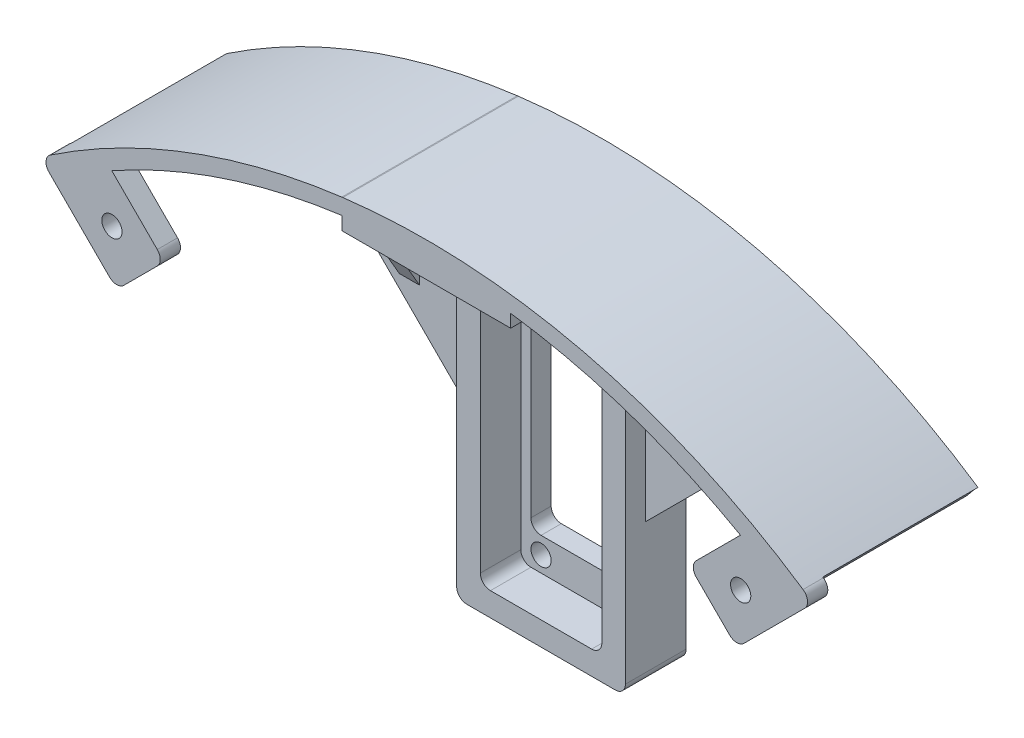
SolidWorks part; units mm, degrees
material "ABS"
ref_plane "Alzado" through (0, 0, 0) normal (0, 0, 1) x (1, 0, 0)
ref_plane "Planta" through (0, 0, 0) normal (0, 1, 0) x (1, 0, 0)
ref_plane "Vista lateral" through (0, 0, 0) normal (1, 0, 0) x (0, 0, -1)
sketch "Croquis1" plane through (0, 0, 0) normal (0, 0, 1) x (1, 0, 0)
  circle A0 centre (0, 0) radius 100
  dimension "D1" = 200
extrude "Saliente-Extruir1" add sketch "Croquis1" along normal blind 3
sketch "Croquis3" plane through (0, 0, 3) normal (0, 0, 1) x (1, 0, 0)
  line L0 (0, 0) -> (190, 0) construction
  circle A0 centre (190, 0) radius 110
  dimension "D1" = 220
  dimension "D2" = 190
extrude "Cortar-Extruir1" cut sketch "Croquis3" against normal blind 3
fillet "Redondeo1" radius 10 2 edges at (89.4737, -44.6594, 1.5) (89.4737, 44.6594, 1.5)
sketch "Croquis5" plane through (0, 0, 3) normal (0, 0, 1) x (1, 0, 0)
  line L0 (0, -100) -> (0, 100) construction
  line L1 (-100, 0) -> (80, 0) construction
  line L2 (0, 0) -> (-70.7107, -70.7107) construction
  line L3 (-70.7107, -70.7107) -> (70.7107, 70.7107) construction
  line L4 (0, 0) -> (-70.7107, 70.7107) construction
  line L5 (-70.7107, 70.7107) -> (70.7107, -70.7107) construction
  line L6 (-70.7107, -70.7107) -> (-58.3363, -83.085) construction
  line L9 (-58.3363, -83.085) -> (-83.085, -58.3363)
  line L11 (-83.085, -58.3363) -> (-65.4074, -40.6586)
  line L12 (-65.4074, -40.6586) -> (-40.6586, -65.4074)
  line L13 (-40.6586, -65.4074) -> (-58.3363, -83.085)
  line L14 (-70.7107, 70.7107) -> (-83.085, 58.3363) construction
  line L15 (-83.085, 58.3363) -> (-100, 0) construction
  line L17 (-83.085, 58.3363) -> (-58.3363, 83.085)
  line L18 (-58.3363, 83.085) -> (-40.6586, 65.4074)
  line L19 (-40.6586, 65.4074) -> (-65.4074, 40.6586)
  line L20 (-65.4074, 40.6586) -> (-83.085, 58.3363)
  line L22 (70.7107, -70.7107) -> (58.3363, -83.085) construction
  line L23 (58.3363, -83.085) -> (0, -100) construction
  line L24 (58.3363, -83.085) -> (83.085, -58.3363)
  line L25 (83.085, -58.3363) -> (65.4074, -40.6586)
  line L26 (65.4074, -40.6586) -> (40.6586, -65.4074)
  line L27 (40.6586, -65.4074) -> (58.3363, -83.085)
  line L28 (70.7107, 70.7107) -> (58.3363, 83.085) construction
  line L29 (58.3363, 83.085) -> (0, 100) construction
  line L30 (58.3363, 83.085) -> (83.085, 58.3363)
  line L31 (83.085, 58.3363) -> (65.4074, 40.6586)
  line L32 (65.4074, 40.6586) -> (40.6586, 65.4074)
  line L33 (40.6586, 65.4074) -> (58.3363, 83.085)
  arc A0 (87.1345, 49.0671) -> (87.1345, -49.0671) centre (0, 0) ccw construction
  arc A1 (87.7193, 40.4803) -> (87.7193, -40.4803) centre (190, 0) ccw construction
  point P36 (0, 0)
  dimension "D2" = 17.5
  dimension "D3" = 25
  dimension "D4" = 35
  dimension "D5" = 25
  dimension "D6" = 35
  dimension "D8" = 25
  dimension "D9" = 17.5
  dimension "D7" = 35
  dimension "D10" = 90
  dimension "D11" = 17.5
  dimension "D12" = 17.5
  dimension "D13" = 35
  dimension "D14" = 25
  dimension "D15" = 134.3503
  dimension "D16" = 100
extrude "Cortar-Extruir6" cut sketch "Croquis5" against normal blind 10
sketch "Croquis12" plane through (0, 0, 3) normal (0, 0, 1) x (1, 0, 0)
  line L0 (-53.033, -53.033) -> (-39.9421, -50.0116) construction
  line L1 (-40.6586, -65.4074) -> (-65.4074, -40.6586) construction
  line L2 (-39.9421, -50.0116) -> (-36.8049, -63.6043) construction
  line L3 (-36.8049, -63.6043) -> (-63.6043, -36.8049) construction
  line L4 (-63.6043, -36.8049) -> (-47.6661, -20.8667) construction
  line L6 (53.033, -53.033) -> (-53.033, 53.033) construction
  line L7 (65.4074, -40.6586) -> (40.6586, -65.4074) construction
  line L8 (-65.4074, 40.6586) -> (-40.6586, 65.4074) construction
  line L9 (36.8049, 63.6043) -> (20.8667, 47.6661) construction
  line L10 (63.6043, 36.8049) -> (36.8049, 63.6043) construction
  line L11 (50.0116, 39.9421) -> (63.6043, 36.8049) construction
  line L12 (53.033, 53.033) -> (50.0116, 39.9421) construction
  line L14 (53.033, -53.033) -> (50.2046, -50.2046) construction
  line L15 (50.2046, -50.2046) -> (36.8049, -63.6043) construction
  line L16 (36.8049, -63.6043) -> (63.6043, -36.8049) construction
  line L17 (63.6043, -36.8049) -> (47.6661, -20.8667) construction
  line L19 (-53.033, -53.033) -> (53.033, 53.033) construction
  line L20 (-36.8049, 63.6043) -> (-20.8667, 47.6661) construction
  line L21 (-63.6043, 36.8049) -> (-36.8049, 63.6043) construction
  line L22 (-50.2046, 50.2046) -> (-63.6043, 36.8049) construction
  line L23 (-53.033, 53.033) -> (-50.2046, 50.2046) construction
  circle A0 centre (-63.6043, -36.8049) radius 1.5
  circle A1 centre (-36.8049, -63.6043) radius 1.5
  circle A2 centre (-47.6661, -20.8667) radius 1.5
  circle A3 centre (-20.8667, -47.6661) radius 1.5
  circle A5 centre (47.6661, 20.8667) radius 1.5
  circle A6 centre (20.8667, 47.6661) radius 1.5
  circle A7 centre (63.6043, 36.8049) radius 1.5
  circle A8 centre (36.8049, 63.6043) radius 1.5
  circle A10 centre (20.8667, -47.6661) radius 1.5
  circle A11 centre (47.6661, -20.8667) radius 1.5
  circle A12 centre (63.6043, -36.8049) radius 1.5
  circle A13 centre (36.8049, -63.6043) radius 1.5
  circle A15 centre (-63.6043, 36.8049) radius 1.5
  circle A16 centre (-36.8049, 63.6043) radius 1.5
  circle A17 centre (-20.8667, 47.6661) radius 1.5
  circle A18 centre (-47.6661, 20.8667) radius 1.5
  dimension "D2" = 3
  dimension "D3" = 3
  dimension "D4" = 4
  dimension "D5" = 4
  dimension "D6" = 3
  dimension "D7" = 3
  dimension "D8" = 37.9
  dimension "D9" = 22.54
  dimension "D10" = 22.54
  dimension "D11" = 37.9
  dimension "D12" = 18.95
  dimension "D13" = 18.95
  dimension "D14" = 3
  dimension "D15" = 3
  dimension "D16" = 3
  dimension "D17" = 3
  dimension "D18" = 37.9
  dimension "D19" = 22.54
  dimension "D20" = 22.54
  dimension "D21" = 37.9
  dimension "D22" = 4
  dimension "D1" = 13.95
extrude "Cortar-Extruir7" cut sketch "Croquis12" against normal through all
sketch "Croquis9" plane through (0, 0, 3) normal (0, 0, 1) x (1, 0, 0)
  line L0 (0, 0) -> (-100, 0) construction
  line L5 (0, 100) -> (0, -100) construction
  line L6 (38.9591, 4) -> (43.4591, 4)
  line L7 (38.9591, 4) -> (38.9591, -4)
  line L8 (38.9591, -4) -> (43.4591, -4)
  line L9 (43.4591, 4) -> (43.4591, -4)
  line L10 (-4, -52) -> (4, -52)
  line L11 (-58.1901, 4) -> (-62.6901, 4)
  line L12 (-58.1901, 4) -> (-58.1901, -4)
  line L13 (-58.1901, -4) -> (-62.6901, -4)
  line L14 (-62.6901, 4) -> (-62.6901, -4)
  line L15 (-4, 56.5) -> (4, 56.5)
  line L16 (-4, 56.5) -> (-4, 52)
  line L17 (-4, 52) -> (4, 52)
  line L18 (4, 56.5) -> (4, 52)
  line L19 (4, -56.5) -> (4, -52)
  line L20 (-4, -56.5) -> (4, -56.5)
  line L21 (-4, -56.5) -> (-4, -52)
  line L22 (0, 0) -> (80, 0) construction
  line L24 (-58.2511, -4) -> (-58.2738, -4) construction
  circle A0 centre (71.9, -4) radius 1.5
  circle A1 centre (35.9591, 4) radius 1.5
  circle A4 centre (71.9591, 4) radius 1.5
  circle A5 centre (35.9, -4) radius 1.5
  arc A6 (-81.9939, 57.2451) -> (-81.9939, -57.2451) centre (0, 0) ccw construction
  arc A7 (87.7193, 40.4803) -> (87.7193, -40.4803) centre (190, 0) ccw construction
  circle A8 centre (-91.1901, 4) radius 1.5
  circle A9 centre (-91.1901, -4) radius 1.5
  circle A10 centre (-55.1901, 4) radius 1.5
  circle A11 centre (-55.1901, -4) radius 1.5
  circle A12 centre (-4, 85) radius 1.5
  circle A13 centre (4, 85) radius 1.5
  circle A14 centre (-4, 49) radius 1.5
  circle A15 centre (4, 49) radius 1.5
  circle A20 centre (-4, -49) radius 1.5
  circle A21 centre (4, -49) radius 1.5
  circle A22 centre (4, -85) radius 1.5
  circle A23 centre (-4, -85) radius 1.5
  arc A24 (87.1345, 49.0671) -> (81.9939, 57.2451) centre (0, 0) ccw construction
  arc A25 (57.2451, 81.9939) -> (-57.2451, 81.9939) centre (0, 0) ccw construction
  dimension "D6" = 35.9
  dimension "D7" = 3
  dimension "D8" = 36
  dimension "D9" = 36
  dimension "D10" = 3
  dimension "D11" = 3
  dimension "D12" = 4
  dimension "D13" = 4
  dimension "D14" = 3
  dimension "D15" = 3
  dimension "D16" = 3
  dimension "D21" = 4
  dimension "D22" = 4
  dimension "D23" = 3
  dimension "D24" = 3
  dimension "D25" = 4
  dimension "D26" = 4
  dimension "D27" = 36
  dimension "D28" = 36
  dimension "D29" = 91.1901
  dimension "D30" = 91.1901
  dimension "D35" = 3
  dimension "D36" = 3
  dimension "D37" = 8
  dimension "D38" = 4
  dimension "D39" = 3
  dimension "D40" = 3
  dimension "D41" = 8
  dimension "D42" = 36
  dimension "D43" = 36
  dimension "D44" = 36
  dimension "D45" = 4
  dimension "D46" = 4
  dimension "D51" = 4
  dimension "D52" = 4
  dimension "D53" = 36.1809
  dimension "D55" = 36
  dimension "D56" = 49
  dimension "D57" = 49
  dimension "D58" = 3
  dimension "D59" = 3
  dimension "D60" = 3
  dimension "D61" = 3
  dimension "D62" = 4.5
  dimension "D32" = 8
  dimension "D64" = 0
  dimension "D69" = 8
  dimension "D70" = 4
  dimension "D71" = 85.0941
  dimension "D72" = 85.0941
  dimension "D17" = 4.5
  dimension "D18" = 8
  dimension "D19" = 3
  dimension "D20" = 0
  dimension "D31" = 3.061
  dimension "D33" = 3
  dimension "D34" = 0
  dimension "D47" = 8
  dimension "D48" = 4.5
  dimension "D49" = 0
  dimension "D50" = 3
  dimension "D54" = 4
  dimension "D63" = 0
  dimension "D65" = 3
  dimension "D66" = 4.5
  dimension "D67" = 8
  dimension "D68" = 3
extrude "Cortar-Extruir5" cut sketch "Croquis9" against normal blind 10
sketch "Croquis13" plane through (0, 0, 3) normal (0, 0, 1) x (1, 0, 0)
  line L0 (-57.2451, 81.9939) -> (-53.7096, 78.4583) construction
  line L1 (-40.6586, 65.4074) -> (-57.2451, 81.9939) construction
  line L2 (57.2451, 81.9939) -> (53.4895, 78.2383) construction
  line L3 (57.2451, 81.9939) -> (40.6586, 65.4074) construction
  line L4 (0, 100) -> (0, 95) construction
  line L5 (-53.7096, 78.4583) -> (-40.6586, 65.4074)
  line L6 (-40.6586, 65.4074) -> (-65.4074, 40.6586)
  line L7 (-65.4074, 40.6586) -> (-81.9939, 57.2451)
  line L8 (-81.9939, -57.2451) -> (-65.4074, -40.6586)
  line L9 (-65.4074, -40.6586) -> (-40.6586, -65.4074)
  line L10 (-40.6586, -65.4074) -> (-57.2451, -81.9939)
  line L12 (81.9939, -57.2451) -> (65.4074, -40.6586)
  line L13 (65.4074, -40.6586) -> (40.6586, -65.4074)
  line L14 (40.6586, -65.4074) -> (57.2451, -81.9939)
  line L15 (53.4895, 78.2383) -> (40.6586, 65.4074)
  line L16 (40.6586, 65.4074) -> (65.4074, 40.6586)
  line L17 (65.4074, 40.6586) -> (81.9939, 57.2451)
  arc A0 (57.2451, 81.9939) -> (-57.2451, 81.9939) centre (0, 0) ccw construction
  arc A1 (-53.7096, 78.4583) -> (53.4895, 78.2383) centre (-0.2711, -0.0867) cw
  arc A2 (-81.9939, 57.2451) -> (-81.9939, -57.2451) centre (0, 0) ccw
  arc A3 (-57.2451, -81.9939) -> (57.2451, -81.9939) centre (0, 0) ccw
  arc A4 (87.7193, -40.4803) -> (87.7193, 40.4803) centre (190, 0) cw
  arc A7 (81.9939, -57.2451) -> (87.7193, -40.4803) centre (81.3824, -47.6762) ccw
  arc A8 (81.9939, 57.2451) -> (87.7193, 40.4803) centre (84.8566, 48.8627) cw
  dimension "D2" = 95
  dimension "D3" = 100
  dimension "D4" = 110
  dimension "D5" = 100
  dimension "D6" = 0.2846
  dimension "D7" = 17.753
  dimension "D1" = 5
extrude "Cortar-Extruir9" cut sketch "Croquis13" against normal through all
sketch "Croquis14" plane through (0, 0, 0) normal (0, 0, -1) x (-1, 0, 0)
  line L1 (45.9314, 70.6802) -> (38.8604, 77.7512)
  line L4 (-45.9314, 70.6802) -> (-38.8604, 77.7512)
  line L6 (45.9314, 70.6802) -> (53.7096, 78.4583)
  line L7 (38.8604, 77.7512) -> (44.8915, 83.7824)
  line L8 (-45.9314, 70.6802) -> (-53.4895, 78.2383)
  line L9 (-38.8604, 77.7512) -> (-44.7026, 83.5935)
  arc A3 (53.7096, 78.4583) -> (-53.4895, 78.2383) centre (0.2711, -0.0867) ccw construction
  arc A4 (53.7096, 78.4583) -> (44.8915, 83.7824) centre (0.2711, -0.0867) ccw
  arc A5 (-53.4895, 78.2383) -> (-44.7026, 83.5935) centre (0.2711, -0.0867) cw
  dimension "D4" = 95
  dimension "D8" = 95
  dimension "D1" = 10.6888
  dimension "D2" = 10
  dimension "D3" = 8.2622
  dimension "D5" = 8.5293
  dimension "D6" = 10
  dimension "D7" = 11
  dimension "D9" = 82.7098
extrude "Saliente-Extruir3" add sketch "Croquis14" against normal blind 3
sketch "Croquis15" plane through (0, 0, 3) normal (0, 0, 1) x (1, 0, 0)
  line L0 (57.2451, 81.9939) -> (45.9314, 70.6802)
  line L1 (45.9314, 70.6802) -> (38.8604, 77.7512)
  line L2 (38.8604, 77.7512) -> (44.7026, 83.5935)
  line L3 (-44.8915, 83.7824) -> (-38.8604, 77.7512)
  line L4 (-38.8604, 77.7512) -> (-45.9314, 70.6802)
  line L5 (-45.9314, 70.6802) -> (-57.2451, 81.9939)
  line L8 (0, 100) -> (0, 97.5) construction
  arc A0 (57.2451, 81.9939) -> (-57.2451, 81.9939) centre (0, 0) ccw
  arc A1 (44.7026, 83.5935) -> (-44.8915, 83.7824) centre (-0.2711, -0.0867) ccw
  dimension "D1" = 100
  dimension "D2" = 95
  dimension "D3" = 2.5
extrude "Saliente-Extruir4" add sketch "Croquis15" along normal blind 23
sketch "Croquis16" plane through (0, 0, 0) normal (0, 0, -1) x (-1, 0, 0)
  line L0 (-44.7026, 83.5935) -> (-46.4704, 85.3612)
  line L1 (44.8915, 83.7824) -> (46.6592, 85.5501)
  arc A0 (-46.4704, 85.3612) -> (46.6592, 85.5501) centre (0.2624, 2.6506) cw
  arc A1 (-44.7026, 83.5935) -> (44.8915, 83.7824) centre (0.2711, -0.0867) cw
  arc A2 (57.2451, 81.9939) -> (-57.2451, 81.9939) centre (0, 0) ccw construction
  dimension "D3" = 95
  dimension "D4" = 95
  dimension "D5" = 2.6635
  dimension "D1" = 2.5
  dimension "D2" = 2.5
extrude "Cortar-Extruir10" cut sketch "Croquis16" against normal through all
sketch "Croquis17" plane through (0, 0, 0) normal (0, 0, -1) x (-1, 0, 0)
  line L0 (-45.9314, 70.6802) -> (-55.4774, 80.2261)
  line L1 (-57.2451, 81.9939) -> (-45.9314, 70.6802) construction
  line L2 (-45.9314, 70.6802) -> (-38.8604, 77.7512)
  line L3 (-38.8604, 77.7512) -> (-46.4704, 85.3612)
  line L4 (46.6592, 85.5501) -> (38.8604, 77.7512)
  line L5 (38.8604, 77.7512) -> (45.9314, 70.6802)
  line L6 (57.2451, 81.9939) -> (55.4774, 80.2261) construction
  line L7 (45.9314, 70.6802) -> (57.2451, 81.9939) construction
  line L8 (55.4774, 80.2261) -> (45.9314, 70.6802)
  line L9 (-46.4704, 85.3612) -> (-55.4774, 80.2261)
  line L10 (55.4774, 80.2261) -> (46.6592, 85.5501)
  dimension "D1" = 13.5
  dimension "D2" = 13.5
extrude "Cortar-Extruir11" cut sketch "Croquis17" against normal blind 23
sketch "Croquis20" plane through (0, 0, 0) normal (0, 0, -1) x (-1, 0, 0)
  line L0 (57.2451, 81.9939) -> (55.4774, 80.2261)
  line L1 (55.4774, 80.2261) -> (46.6592, 85.5501) construction
  line L2 (55.5571, 83.0598) -> (53.7616, 81.262)
  line L3 (-57.2451, 81.9939) -> (-55.4774, 80.2261)
  line L4 (-46.4704, 85.3612) -> (-55.4774, 80.2261) construction
  line L5 (-53.927, 81.11) -> (-55.5535, 83.0598)
  arc A0 (55.4774, 80.2261) -> (53.7616, 81.262) centre (55.1321, 81.5932) cw
  arc A1 (57.2451, 81.9939) -> (55.5571, 83.0598) centre (55.8682, 81.6828) ccw
  arc A2 (57.2451, 81.9939) -> (-57.2451, 81.9939) centre (0, 0) ccw construction
  arc A3 (-55.4774, 80.2261) -> (-53.927, 81.11) centre (-55.1441, 81.4432) ccw
  arc A4 (-57.2451, 81.9939) -> (-55.5535, 83.0598) centre (-55.8663, 81.681) cw
  dimension "D1" = 1.4117
  dimension "D2" = 1.41
  dimension "D4" = 0.736
  dimension "D5" = 98.9613
  dimension "D7" = 0.8923
  dimension "D8" = 98.9588
  dimension "D9" = 0.7222
  dimension "D10" = 1.2619
  dimension "D3" = 2.5409
  dimension "D6" = 2.5391
extrude "Cortar-Extruir14" cut sketch "Croquis20" against normal blind 23
sketch "Croquis21" plane through (0, 0, 23) normal (0, 0, -1) x (-1, 0, 0)
  line L0 (-57.1062, 81.8549) -> (-50.0351, 74.7839) construction
  line L1 (-57.2451, 81.9939) -> (-45.9314, 70.6802) construction
  line L2 (-50.0351, 74.7839) -> (-46.4996, 78.3194) construction
  line L3 (-45.9314, 70.6802) -> (-38.8604, 77.7512) construction
  line L4 (-38.8604, 77.7512) -> (-46.4704, 85.3612) construction
  line L5 (57.2451, 81.9939) -> (50.1741, 74.9228) construction
  line L6 (45.9314, 70.6802) -> (57.2451, 81.9939) construction
  line L7 (50.1741, 74.9228) -> (46.6385, 78.4583) construction
  line L8 (38.8604, 77.7512) -> (45.9314, 70.6802) construction
  line L9 (46.6592, 85.5501) -> (38.8604, 77.7512) construction
  circle A0 centre (-46.4996, 78.3194) radius 1.5
  circle A1 centre (46.6385, 78.4583) radius 1.5
  dimension "D1" = 3
  dimension "D2" = 5.8035
  dimension "D3" = 5
  dimension "D4" = 3
  dimension "D5" = 6
  dimension "D6" = 5
extrude "Cortar-Extruir15" cut sketch "Croquis21" against normal through all
sketch "Croquis23" plane through (0, 0, 26) normal (0, 0, 1) x (1, 0, 0)
  line L0 (-0.0697, 97.6504) -> (-0.0697, 67.6504) construction
  line L2 (-12.5697, 39.2244) -> (12.4303, 39.2244)
  line L3 (-12.5697, 39.2244) -> (-12.5697, 99.2244)
  line L4 (-12.5697, 99.2244) -> (12.4303, 99.2244)
  line L5 (12.4303, 39.2244) -> (12.4303, 99.2244)
  arc A0 (46.4704, 85.3612) -> (-46.6592, 85.5501) centre (-0.2624, 2.6506) ccw construction
  arc A1 (57.2451, 81.9939) -> (-57.2451, 81.9939) centre (0, 0) ccw construction
  dimension "D1" = 30
  dimension "D2" = 25
  dimension "D3" = 12.5
  dimension "D4" = 60
extrude "Saliente-Extruir5" add sketch "Croquis23" against normal through all
sketch "Croquis24" plane through (0, 39.2244, 0) normal (0, -1, 0) x (-1, 0, 0)
  line L1 (12.5697, -26) -> (-12.4303, -26)
  line L2 (12.5697, -26) -> (12.5697, -9)
  line L3 (12.5697, -9) -> (-12.4303, -9)
  line L4 (-12.4303, -26) -> (-12.4303, -9)
  dimension "D1" = 25
  dimension "D2" = 17
extrude "Cortar-Extruir16" cut sketch "Croquis24" against normal blind 55.67
sketch "Croquis25" plane through (0, 0, 9) normal (0, 0, 1) x (1, 0, 0)
  line L0 (-12.5697, 94.8944) -> (-12.5697, 39.2244) construction
  line L1 (-9.0697, 91.3944) -> (8.9303, 91.3944)
  line L2 (-9.0697, 91.3944) -> (-9.0697, 42.7244)
  line L3 (-9.0697, 42.7244) -> (8.9303, 42.7244)
  line L4 (8.9303, 91.3944) -> (8.9303, 42.7244)
  line L5 (12.4303, 94.8944) -> (12.4303, 39.2244) construction
  line L6 (12.4303, 94.8944) -> (-12.5697, 94.8944) construction
  line L7 (-12.5697, 39.2244) -> (12.4303, 39.2244) construction
  dimension "D1" = 3.5
  dimension "D2" = 3.5
  dimension "D3" = 3.5
  dimension "D4" = 3.5
extrude "Cortar-Extruir17" cut sketch "Croquis25" against normal blind 6
sketch "Croquis26" plane through (0, 0, 3) normal (0, 0, 1) x (1, 0, 0)
  line L0 (-8.5697, 89.5694) -> (-8.5697, 42.5694) construction
  line L1 (-8.5697, 42.5694) -> (8.4303, 42.5694) construction
  line L2 (-8.5697, 89.5694) -> (8.4303, 89.5694) construction
  line L3 (8.4303, 89.5694) -> (8.4303, 42.5694) construction
  line L4 (8.9303, 42.7244) -> (8.9303, 91.3944) construction
  line L6 (8.9303, 91.3944) -> (-9.0697, 91.3944) construction
  line L8 (-7.5697, 84.5694) -> (7.4303, 84.5694)
  line L9 (-7.5697, 84.5694) -> (-7.5697, 47.5694)
  line L10 (-7.5697, 47.5694) -> (7.4303, 47.5694)
  line L11 (7.4303, 84.5694) -> (7.4303, 47.5694)
  line L12 (-3.0697, 88.5694) -> (2.9303, 88.5694)
  line L13 (-3.0697, 88.5694) -> (-3.0697, 84.5694)
  line L14 (-3.0697, 84.5694) -> (2.9303, 84.5694)
  line L15 (2.9303, 88.5694) -> (2.9303, 84.5694)
  circle A0 centre (-6.0697, 87.0694) radius 1.5
  circle A1 centre (5.9303, 87.0694) radius 1.5
  circle A2 centre (-6.0697, 45.0694) radius 1.5
  circle A3 centre (5.9303, 45.0694) radius 1.5
  dimension "D5" = 3
  dimension "D6" = 3
  dimension "D7" = 2.5
  dimension "D8" = 2.5
  dimension "D9" = 2.5
  dimension "D10" = 2.5
  dimension "D11" = 3
  dimension "D12" = 2.5
  dimension "D13" = 2.5
  dimension "D14" = 2.5
  dimension "D15" = 2.5
  dimension "D16" = 3
  dimension "D1" = 47
  dimension "D2" = 17
  dimension "D3" = 0.5
  dimension "D4" = 1.825
  dimension "D17" = 37
  dimension "D18" = 5
  dimension "D19" = 0
  dimension "D20" = 6
  dimension "D21" = 3
  dimension "D22" = 15
  dimension "D23" = 1
  dimension "D24" = 4
extrude "Cortar-Extruir18" cut sketch "Croquis26" against normal through all contours L11 L8 L9 L10 | A2 | L15 L10 L13 L14 | A3 | A0 | A1 region at (-0.0697, 66.0694, 3) region at (-0.0697, 86.5694, 3) region at (-6.0697, 87.0694, 3) region at (5.9303, 87.0694, 3) region at (-6.0697, 45.0694, 3) region at (5.9303, 45.0694, 3)
fillet "Redondeo2" radius 1.5 20 edges at (38.8604, 77.7512, 24.5) (57.2451, 81.9939, 24.5) (45.9314, 70.6802, 24.5) (-38.8604, 77.7512, 24.5) (-45.9314, 70.6802, 24.5) (-57.2451, 81.9939, 24.5) (8.9303, 42.7244, 6) (-9.0697, 42.7244, 6) (8.9303, 91.3944, 6) (-9.0697, 91.3944, 6) (7.4303, 47.5694, 1.5) (2.9303, 84.5694, 1.5) (-3.0697, 84.5694, 1.5) (-3.0697, 88.5694, 1.5) (7.4303, 84.5694, 1.5) (-7.5697, 84.5694, 1.5) (2.9303, 88.5694, 1.5) (-7.5697, 47.5694, 1.5) (-12.5697, 39.2244, 4.5) (12.4303, 39.2244, 4.5)
ref_plane "Plano6" through (0, 0, 4.5) normal (0, 0, -1) x (-1, 0, 0)
sketch "Croquis31" plane through (0, 0, 4.5) normal (0, 0, -1) x (-1, 0, 0)
  line L0 (12.5697, 60.2577) -> (40.854, 88.5419)
  line L1 (12.5697, 96.85) -> (12.5697, 40.7244) construction
  arc A0 (46.6592, 85.5501) -> (12.5697, 96.85) centre (0.2624, 2.6506) ccw construction
  dimension "D1" = 45
  dimension "D2" = 40
rib "Nervio2" sketch "Croquis31" sketch "Croquis31" thickness 3 extrusion direction parallel to sketch draft on no parameters "D1"=3
sketch "Croquis32" plane through (0, 0, 4.5) normal (0, 0, -1) x (-1, 0, 0)
  line L0 (-12.4303, 60.0745) -> (-40.7146, 88.3588)
  line L1 (-12.4303, 40.7244) -> (-12.4303, 96.7989) construction
  arc A0 (-12.4303, 96.7989) -> (-46.4704, 85.3612) centre (0.2624, 2.6506) ccw construction
  dimension "D1" = 40
  dimension "D2" = 45
rib "Nervio4" sketch "Croquis32" sketch "Croquis32" thickness 3 extrusion direction parallel to sketch draft on no parameters "D1"=3
ref_plane "Plano8" through (23, 0, 0) normal (1, 0, 0) x (0, 0, -1)
sketch "Croquis36" plane through (23, 0, 0) normal (1, 0, 0) x (0, 0, -1)
  line L0 (-6, 74.2166) -> (-19.5, 97.5993)
  line L1 (-6, 60.0745) -> (-6, 88.3588) construction
  dimension "D1" = 27
  dimension "D2" = 30
rib "Nervio5" sketch "Croquis36" sketch "Croquis36" thickness 3 extrusion direction parallel to sketch draft on no parameters "D1"=3
ref_plane "Plano9" through (-22.5697, 0, 0) normal (-1, 0, 0) x (0, 0, 1)
sketch "Croquis37" plane through (-22.5697, 0, 0) normal (-1, 0, 0) x (0, 0, 1)
  line L0 (6, 73.6605) -> (18, 94.4451)
  line L14 (6, 60.2577) -> (6, 88.5419) construction
  line L16 (6, 88.5419) -> (6, 96.85) construction
  point P4 (0, 0)
  point P6 (0, 0)
  point P7 (0, 0)
  dimension "D1" = 12
  dimension "D2" = 30
rib "Nervio10" sketch "Croquis37" sketch "Croquis37" thickness 3 extrusion direction parallel to sketch draft on no parameters "D1"=3
